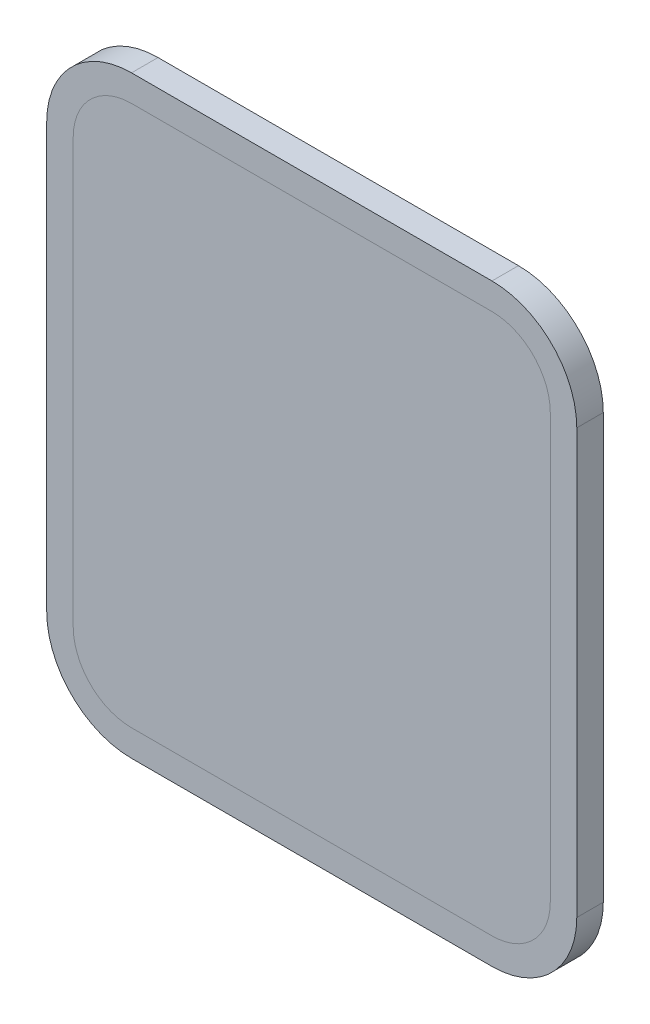
SolidWorks part; units mm, degrees
material "Glass"
ref_plane "Front Plane" through (0, 0, 0) normal (0, 0, 1) x (1, 0, 0)
ref_plane "Top Plane" through (0, 0, 0) normal (0, 1, 0) x (1, 0, 0)
ref_plane "Right Plane" through (0, 0, 0) normal (1, 0, 0) x (0, 0, -1)
sketch "Sketch1" plane through (0, 0, 0) normal (0, 0, 1) x (1, 0, 0)
  line L0 (160, 0) -> (840, 0)
  line L1 (1000, 160) -> (1000, 960)
  line L2 (840, 1120) -> (160, 1120)
  line L3 (0, 960) -> (0, 160)
  arc A0 (160, 0) -> (0, 160) centre (160, 160) cw
  arc A1 (840, 0) -> (1000, 160) centre (840, 160) ccw
  arc A2 (1000, 960) -> (840, 1120) centre (840, 960) ccw
  arc A3 (160, 1120) -> (0, 960) centre (160, 960) ccw
  point P7 (0, 0)
  point P10 (1000, 0)
  point P15 (0, 1120)
  dimension "D3" = 160
  dimension "D1" = 1000
  dimension "D2" = 1120
extrude "Boss-Extrude1" add sketch "Sketch1" along normal blind 50
sketch "Sketch2" plane through (0, 1120, 0) normal (0, 1, 0) x (1, 0, 0)
  line L0 (160, -25) -> (840, -25) construction
  line L1 (160, -50) -> (160, 0) construction
  line L2 (840, -50) -> (840, 0) construction
  line L3 (500, 0) -> (500, -50) construction
  line L4 (840, 0) -> (160, 0) construction
  line L5 (840, -50) -> (160, -50) construction
  circle A0 centre (500, -25) radius 50
  dimension "D1" = 100
sketch "Sketch3" plane through (0, 0, 50) normal (0, 0, 1) x (1, 0, 0)
  line L8 (160, 50) -> (840, 50)
  line L9 (950, 160) -> (950, 960)
  line L10 (840, 1070) -> (160, 1070)
  line L11 (50, 960) -> (50, 160)
  line L12 (160, 50) -> (840, 50)
  line L13 (950, 160) -> (950, 960)
  line L14 (840, 1070) -> (160, 1070)
  line L15 (50, 960) -> (50, 160)
  arc A8 (50, 160) -> (160, 50) centre (160, 160) ccw
  arc A9 (840, 50) -> (950, 160) centre (840, 160) ccw
  arc A10 (950, 960) -> (840, 1070) centre (840, 960) ccw
  arc A11 (160, 1070) -> (50, 960) centre (160, 960) ccw
  arc A12 (50, 160) -> (160, 50) centre (160, 160) ccw
  arc A13 (840, 50) -> (950, 160) centre (840, 160) ccw
  arc A14 (950, 960) -> (840, 1070) centre (840, 960) ccw
  arc A15 (160, 1070) -> (50, 960) centre (160, 960) ccw
  dimension "D1" = 50
extrude "Cut-Extrude1" cut sketch "Sketch3" against normal up to next
extrude "Boss-Extrude3" add sketch "Sketch3<2>" against normal blind 50 separate body
sketch "Sketch3<2>" plane through (0, 0, 50) normal (0, 0, 1) x (1, 0, 0) same geometry as "Sketch3"
